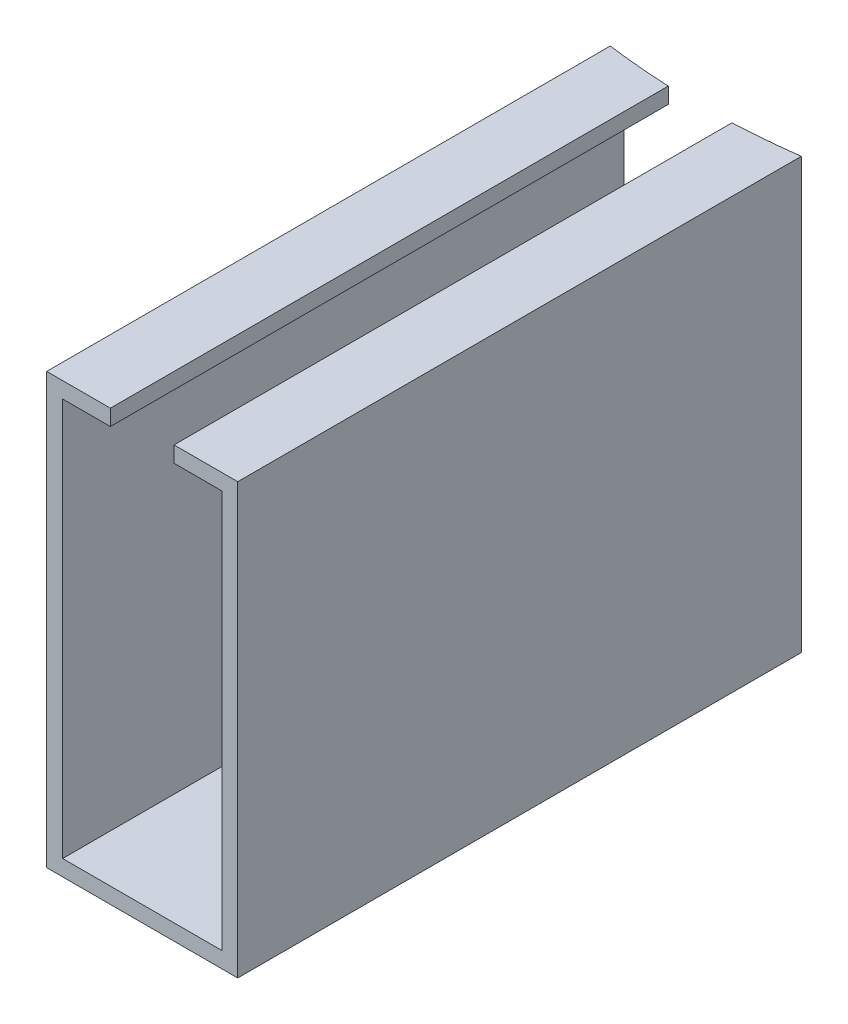
SolidWorks part; units mm, degrees
material "ABS"
ref_plane "正面" through (0, 0, 0) normal (0, 0, 1) x (1, 0, 0)
ref_plane "平面" through (0, 0, 0) normal (0, 1, 0) x (1, 0, 0)
ref_plane "右側面" through (0, 0, 0) normal (1, 0, 0) x (0, 0, -1)
sketch "ｽｹｯﾁ1" plane through (0, 0, 0) normal (0, 0, 1) x (1, 0, 0)
  line L0 (0, 0) -> (5, 0)
  line L1 (0, 0) -> (0, 12.5)
  line L3 (-0.5, 12.5) -> (-0.5, -0.5)
  line L4 (-0.5, -0.5) -> (5.5, -0.5)
  line L5 (5.5, -0.5) -> (5.5, 12.5)
  line L7 (5, 12.5) -> (5, 0)
  line L8 (-0.5, 12.5) -> (-0.5, 13)
  line L9 (-0.5, 13) -> (1.5, 13)
  line L10 (1.5, 13) -> (1.5, 12.5)
  line L11 (1.5, 12.5) -> (0, 12.5)
  line L12 (5.5, 12.5) -> (5.5, 13)
  line L13 (5.5, 13) -> (3.5, 13)
  line L14 (3.5, 13) -> (3.5, 12.5)
  line L15 (3.5, 12.5) -> (5, 12.5)
  dimension "D1" = 5
  dimension "D2" = 12.5
  dimension "D3" = 0.5
  dimension "D4" = 13
  dimension "D5" = 6
  dimension "D6" = 13
  dimension "D7" = 0.5
  dimension "D8" = 0.5
  dimension "D9" = 2
  dimension "D10" = 2
  dimension "D11" = 0.5
extrude "ﾎﾞｽ - 押し出し1" add sketch "ｽｹｯﾁ1" along normal blind 40
sketch "ｽｹｯﾁ2" plane through (0, -0.5, 0) normal (0, -1, 0) x (1, 0, 0)
  line L0 (2.5, 40) -> (2.5, 0)
  line L1 (-0.5, 40) -> (5.5, 40) construction
  line L2 (-0.5, 0) -> (5.5, 0) construction
  circle A0 centre (2.5, 0) radius 22.5
  dimension "D1" = 45
extrude "ｶｯﾄ - 押し出し1" cut sketch "ｽｹｯﾁ2" against normal blind 40 contours A0
